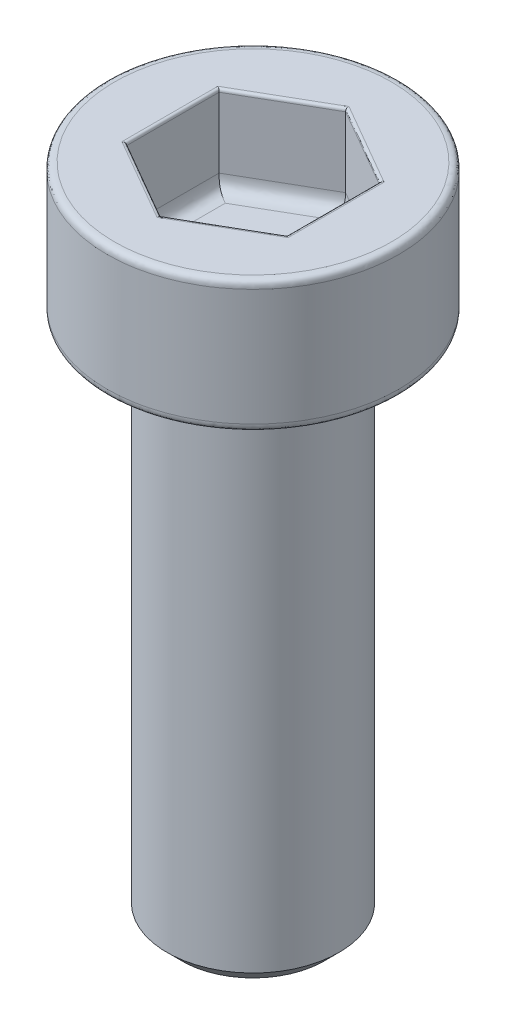
SolidWorks part; units mm, degrees
ref_plane "Front Plane" through (0, 0, 0) normal (0, 0, 1) x (1, 0, 0)
ref_plane "Top Plane" through (0, 0, 0) normal (0, 1, 0) x (1, 0, 0)
ref_plane "Right Plane" through (0, 0, 0) normal (1, 0, 0) x (0, 0, -1)
sketch "Sketch2" plane through (0, 0, 0) normal (1, 0, 0) x (0, 0, -1)
  line L0 (0, 0) -> (0, 45)
  line L1 (0, 45) -> (10, 45)
  line L2 (10, 45) -> (10, 36)
  line L3 (10, 36) -> (5.9, 36)
  line L4 (5.9, 36) -> (5.9, 0)
  line L5 (5.9, 0) -> (0, 0)
  dimension "D1" = 5.9
  dimension "D2" = 10
  dimension "D3" = 9
  dimension "D4" = 45
revolve "Revolve1" add sketch "Sketch2" angle 360 about L0
chamfer "Chamfer1" distance 1 angle 45 1 edges at (0, 0, -5.9)
sketch "Sketch3" plane through (0, 45, 0) normal (0, 1, 0) x (1, 0, 0)
  line L1 (0, 6.3509) -> (-5.5, 3.1754)
  line L2 (-5.5, 3.1754) -> (-5.5, -3.1754)
  line L3 (-5.5, -3.1754) -> (0, -6.3509)
  line L4 (0, -6.3509) -> (5.5, -3.1754)
  line L5 (5.5, -3.1754) -> (5.5, 3.1754)
  line L6 (5.5, 3.1754) -> (0, 6.3509)
  circle A0 centre (0, 0) radius 5.5 construction
  dimension "D1" = 11
extrude "Cut-Extrude1" cut sketch "Sketch3" against normal blind 6
fillet "Fillet1" radius 1 6 edges at (5.5, 39, 0) (2.75, 39, 4.7631) (-2.75, 39, 4.7631) (-5.5, 39, 0) (-2.75, 39, -4.7631) (2.75, 39, -4.7631) curvature continuous yes
fillet "Fillet2" radius 0.5 2 edges at (0, 36, -10) (0, 45, -10) curvature continuous yes
ref_axis "Axis1" through (0, 36, 0) along (0, -1, 0)
fillet "Fillet3" radius 0.2 6 edges at (-5.5, 45, 0) (-2.75, 45, 4.7631) (2.75, 45, 4.7631) (5.5, 45, 0) (2.75, 45, -4.7631) (-2.75, 45, -4.7631) curvature continuous yes
